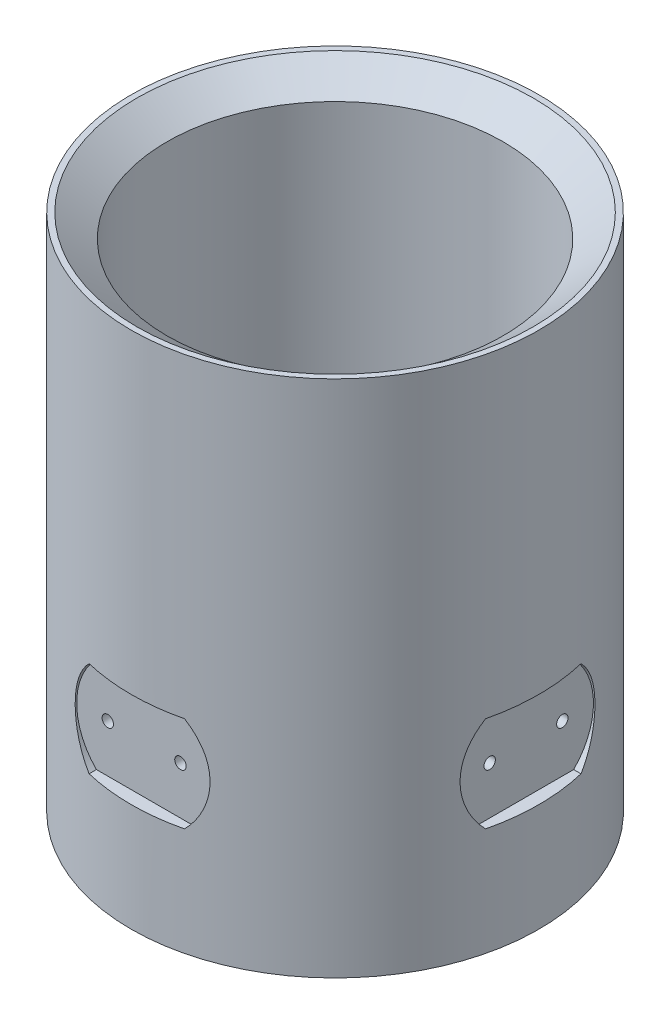
SolidWorks part; units mm, degrees
ref_plane "Front Plane" through (0, 0, 0) normal (0, 0, 1) x (1, 0, 0)
ref_plane "Top Plane" through (0, 0, 0) normal (0, 1, 0) x (1, 0, 0)
ref_plane "Right Plane" through (0, 0, 0) normal (1, 0, 0) x (0, 0, -1)
sketch "Sketch2" plane through (0, 0, 0) normal (0, 1, 0) x (1, 0, 0)
  circle A0 centre (0, 0) radius 39.3
  circle A1 centre (0, 0) radius 32.4
  dimension "D1" = 78.6
  dimension "D2" = 64.8
extrude "Boss-Extrude1" add sketch "Sketch2" along normal blind 100
sketch "Sketch3" plane through (0, 0, 0) normal (0, 0, 1) x (1, 0, 0)
  line L1 (9.1924, 39.1924) -> (-9.1924, 39.1924)
  line L3 (-9.1924, 20.8076) -> (9.1924, 20.8076)
  arc A0 (-9.1924, 39.1924) -> (-9.1924, 20.8076) centre (0, 30) ccw
  arc A1 (9.1924, 20.8076) -> (9.1924, 39.1924) centre (0, 30) ccw
  dimension "D1" = 26
  dimension "D2" = 30
extrude "Cut-Extrude1" cut sketch "Sketch3" against normal blind 2.5 from offset 39.3
ref_axis "Axis1" through (0, 100, 0) along (0, -1, 0)
sketch "Sketch4" plane through (0, 0, 36.8) normal (0, 0, 1) x (1, 0, 0)
  circle A2 centre (7, 30) radius 1.1
  circle A3 centre (-7, 30) radius 1.1
  dimension "D1" = 2.2
  dimension "D2" = 2.2
extrude "Cut-Extrude2" cut sketch "Sketch4" against normal blind 3
pattern_circular "CirPattern1" count 4 over 360 about axis through (0, 100, 0) along (0, -1, 0) of "Cut-Extrude1", "Cut-Extrude2"
chamfer "Chamfer1" distance 5.8 distance2 4.4 1 edges at (0, 100, 32.4) first distance on face at (0, 100, 39.3)
